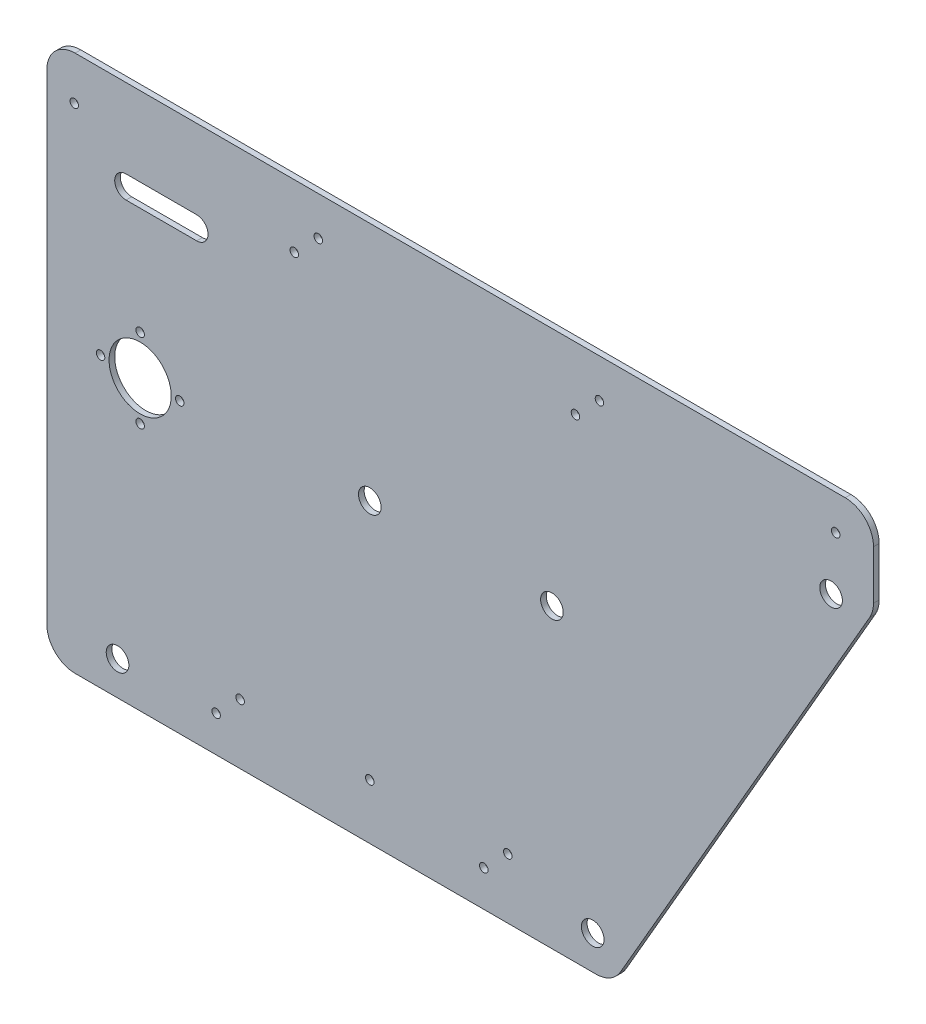
SolidWorks part; units mm, degrees
ref_plane "Front Plane" through (0, 0, 0) normal (0, 0, 1) x (1, 0, 0)
ref_plane "Top Plane" through (0, 0, 0) normal (0, 1, 0) x (1, 0, 0)
ref_plane "Right Plane" through (0, 0, 0) normal (1, 0, 0) x (0, 0, -1)
sketch "Sketch1" plane through (0, 0, 0) normal (0, 0, 1) x (1, 0, 0)
  line L0 (100, 80) -> (192.376, 80)
  line L1 (-100, -80) -> (100, -80)
  line L2 (-100, -80) -> (-100, 80)
  line L3 (-100, 80) -> (100, 80)
  line L4 (100, -80) -> (100, 80)
  line L5 (-100, -80) -> (100, 80) construction
  line L6 (-100, 80) -> (100, -80) construction
  line L7 (192.376, 80) -> (100, -80)
  line L8 (100, 80) -> (100, -80)
  line L10 (-100, 80) -> (192.376, 80)
  line L11 (-100, 80) -> (-100, 110)
  line L12 (-100, 110) -> (192.376, 110)
  line L13 (192.376, 80) -> (192.376, 110)
  point P0 (0, 0)
  dimension "D1" = 160
  dimension "D2" = 200
  dimension "D3" = 30
  dimension "D4" = 30
extrude "Boss-Extrude1" add sketch "Sketch1" along normal blind 2 contours L1 L4 L3 L2 | L7 L0 L4 | L11 L10 L13 L12 region at (0, 0, 0) region at (130.792, 26.6667, 0)
fillet "Fillet1" radius 10 5 edges at (100, -80, 1) (-100, -80, 1) (192.376, 110, 1) (192.376, 80, 1) (-100, 110, 1)
sketch "Sketch2" plane through (0, 0, 2) normal (0, 0, 1) x (1, 0, 0)
  line L0 (-90, -80) -> (94.2265, -80) construction
  line L1 (191.0363, 77.6795) -> (102.8868, -75) construction
  line L3 (-100, -70) -> (-100, 100) construction
  line L4 (-72, 78) -> (-47, 78) construction
  line L7 (-90, 110) -> (182.376, 110) construction
  line L9 (-72, 82) -> (-47, 82)
  line L10 (-72, 74) -> (-47, 74)
  line L11 (-100, -70) -> (-100, 100) construction
  circle A0 centre (93.0718, -68) radius 4
  circle A1 centre (177.3649, 78) radius 4
  circle A2 centre (-67, 22) radius 11
  circle A3 centre (-75, -68) radius 4
  circle A4 centre (-53, 22) radius 1.5
  circle A5 centre (-67, 36) radius 1.5
  circle A6 centre (-81, 22) radius 1.5
  circle A7 centre (-67, 8) radius 1.5
  circle A11 centre (54.5495, -67.2426) radius 1.5
  circle A12 centre (63.0348, -58.7574) radius 1.5
  circle A13 centre (14.2259, -60.5) radius 1.5
  circle A14 centre (-40.1271, -67.2426) radius 1.5
  circle A15 centre (-31.6419, -58.7574) radius 1.5
  circle A16 centre (-90.2956, 94.5) radius 1.5
  circle A17 centre (-12.4828, 87.7574) radius 1.5
  circle A18 centre (-3.9975, 96.2426) radius 1.5
  circle A19 centre (86.9654, 87.7574) radius 1.5
  circle A20 centre (95.4507, 96.2426) radius 1.5
  circle A21 centre (41.9695, 24.7574) radius 1.5 construction
  circle A22 centre (50.4548, 33.2426) radius 1.5 construction
  circle A23 centre (-45.6014, 24.7574) radius 1.5 construction
  circle A24 centre (-37.1161, 33.2426) radius 1.5 construction
  circle A25 centre (116.8113, 24.7574) radius 1.5 construction
  circle A26 centre (125.2966, 33.2426) radius 1.5 construction
  circle A27 centre (78.6382, 25) radius 4
  circle A28 centre (14.2259, 25) radius 4
  arc A29 (-72, 82) -> (-72, 74) centre (-72, 78) ccw
  arc A30 (-47, 74) -> (-47, 82) centre (-47, 78) ccw
  circle A31 centre (178.9933, 97.6095) radius 1.5
  point P26 (-59.5, 78)
  dimension "D3" = 8
  dimension "D4" = 8
  dimension "D9" = 22
  dimension "D10" = 8
  dimension "D12" = 3
  dimension "D13" = 3
  dimension "D14" = 3
  dimension "D15" = 3
  dimension "D16" = 14
  dimension "D20" = 8
  dimension "D22" = 4
  dimension "D25" = 3
  dimension "D26" = 3
  dimension "D29" = 8
  dimension "D28" = 3
  dimension "D1" = 12
  dimension "D2" = 12
  dimension "D5" = 32
  dimension "D6" = 12
  dimension "D7" = 88
  dimension "D8" = 33
  dimension "D11" = 12
  dimension "D17" = 14
  dimension "D18" = 14
  dimension "D19" = 14
  dimension "D21" = 85
  dimension "D23" = 28
  dimension "D24" = 25
  dimension "D27" = 25
extrude "Cut-Extrude1" cut sketch "Sketch2" against normal blind 3
